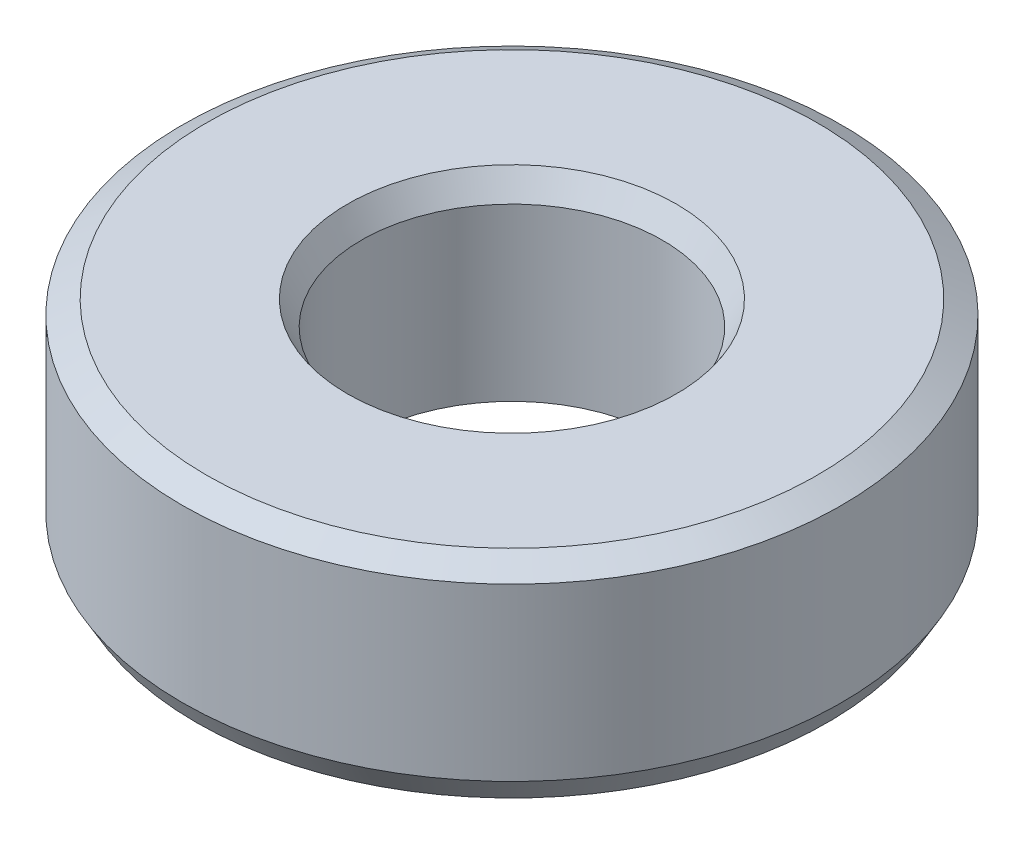
SolidWorks part; units mm, degrees
ref_plane "Front Plane" through (0, 0, 0) normal (0, 0, 1) x (1, 0, 0)
ref_plane "Top Plane" through (0, 0, 0) normal (0, 1, 0) x (1, 0, 0)
ref_plane "Right Plane" through (0, 0, 0) normal (1, 0, 0) x (0, 0, -1)
sketch "Sketch1" plane through (0, 0, 0) normal (0, 1, 0) x (1, 0, 0)
  circle A0 centre (0, 0) radius 37.5
  dimension "SLEEVE_OD" = 75
extrude "Boss-Extrude1" add sketch "Sketch1" along normal blind 23.789
sketch "Sketch2" plane through (0, 0, 0) normal (0, 1, 0) x (1, 0, 0)
  circle A0 centre (0, 0) radius 17.123
  dimension "BORE_D" = 34.246
extrude "Cut-Extrude1" cut sketch "Sketch2" along normal through all
chamfer "Chamfer1" distance 1.5919 angle 60 4 edges at (0, 23.789, 17.123) (0, 0, 17.123) (0, 0, 37.5) (0, 23.789, 37.5) first distance on face at (0, 23.789, 17.123) first distance on face at (0, 0, 17.123) first distance on face at (0, 23.789, 37.5)
